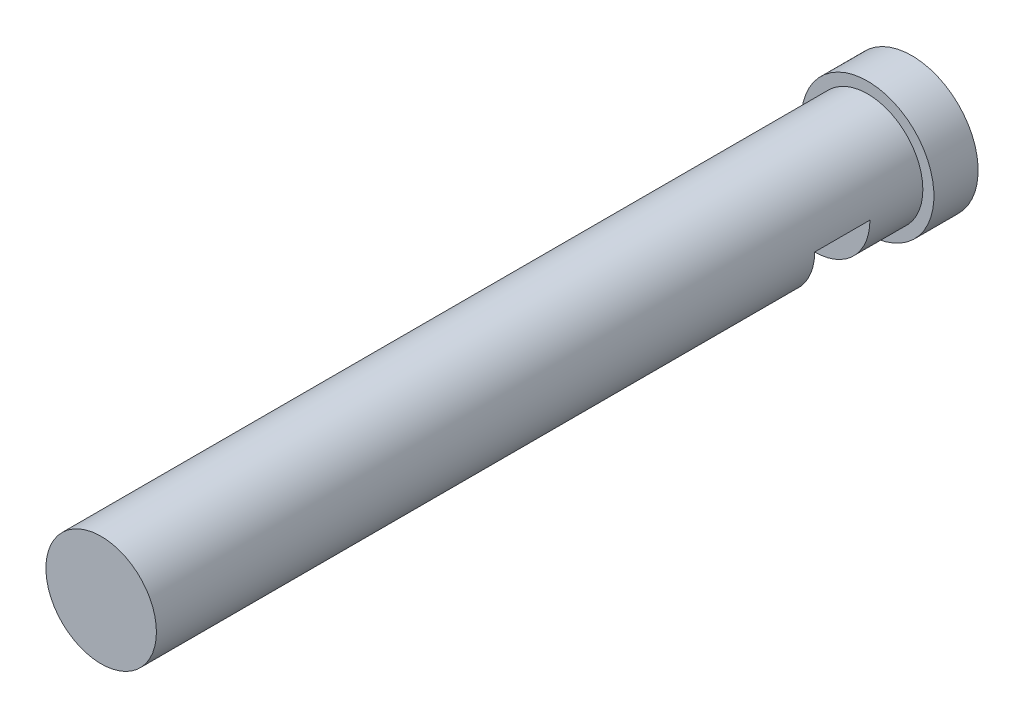
SolidWorks part; units mm, degrees
material "AISI 1020 Steel, Cold Rolled"
ref_plane "Front Plane" through (0, 0, 0) normal (0, 0, 1) x (1, 0, 0)
ref_plane "Top Plane" through (0, 0, 0) normal (0, 1, 0) x (1, 0, 0)
ref_plane "Right Plane" through (0, 0, 0) normal (1, 0, 0) x (0, 0, -1)
sketch "Sketch1" plane through (0, 0, 0) normal (0, 0, 1) x (1, 0, 0)
  circle A0 centre (0, 0) radius 6.35
  dimension "D1" = 12.7
extrude "Boss-Extrude1" add sketch "Sketch1" along normal blind 6.0833
sketch "Sketch4" plane through (0, 0, 0) normal (0, 0, -1) x (-1, 0, 0)
  circle A0 centre (0, 0) radius 7.62
  dimension "D1" = 15.24
extrude "Boss-Extrude2" add sketch "Sketch4" along normal blind 5.08
ref_plane "Plane6" through (0, 0, 3.175) normal (0, 0, -1) x (-1, 0, 0)
sketch "Sketch12" plane through (0, 0, 6.0833) normal (0, 0, 1) x (1, 0, 0)
  line L0 (0, -6.35) -> (6.35, 0)
  circle A0 centre (0, 0) radius 6.35 construction
  arc A1 (0, -6.35) -> (6.35, 0) centre (0, 0) cw
extrude "Boss-Extrude3" add sketch "Sketch12" along normal blind 6.35
sketch "Sketch13" plane through (0, 0, 12.4333) normal (0, 0, 1) x (1, 0, 0)
  circle A0 centre (0, 0) radius 6.35
extrude "Boss-Extrude4" add sketch "Sketch13" along normal blind 75.6361
